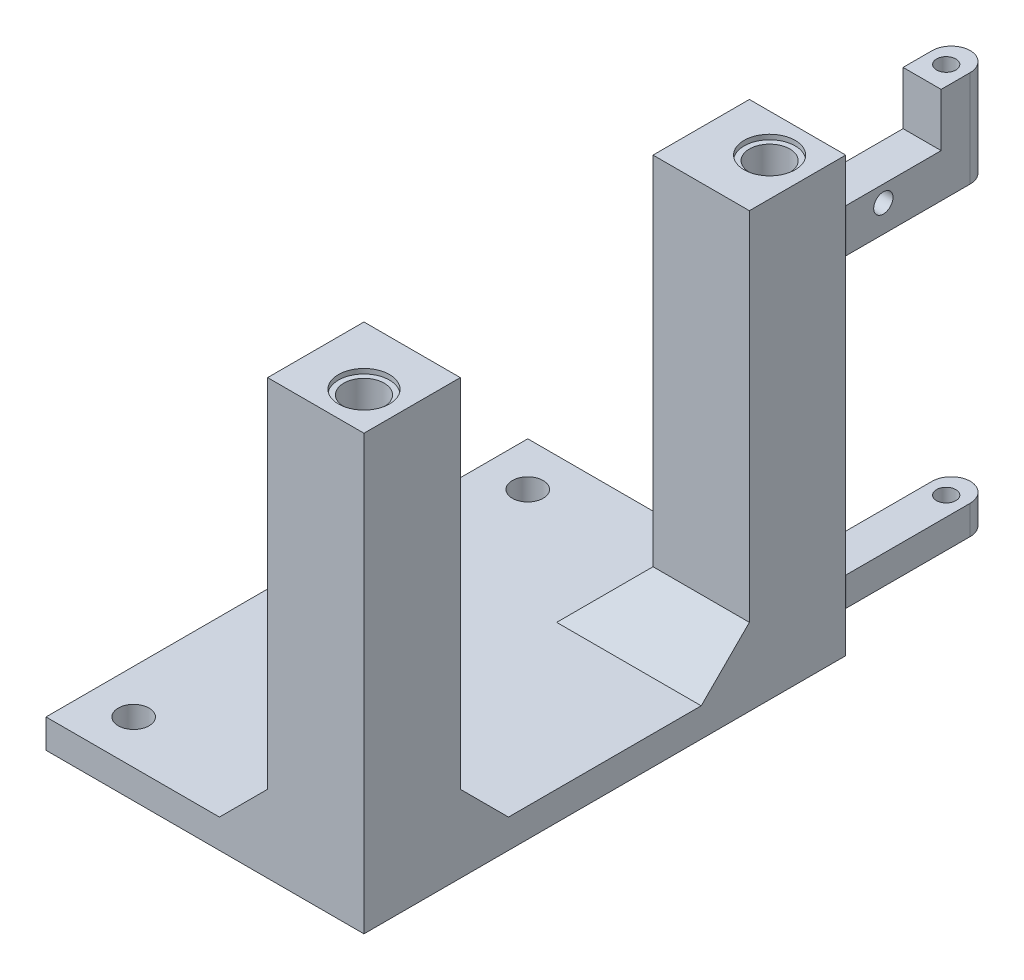
SolidWorks part; units mm, degrees
ref_plane "Front Plane" through (0, 0, 0) normal (0, 0, 1) x (1, 0, 0)
ref_plane "Top Plane" through (0, 0, 0) normal (0, 1, 0) x (1, 0, 0)
ref_plane "Right Plane" through (0, 0, 0) normal (1, 0, 0) x (0, 0, -1)
sketch "Sketch1" plane through (0, 0, 0) normal (0, 1, 0) x (1, 0, 0)
  line L1 (-6.5124, 9.686) -> (1.4876, 9.686)
  line L2 (-6.5124, 9.686) -> (-6.5124, -40.314)
  line L3 (-6.5124, -40.314) -> (1.4876, -40.314)
  line L4 (1.4876, 9.686) -> (1.4876, -40.314)
  line L5 (1.4876, 9.686) -> (26.4876, 9.686)
  line L6 (1.4876, 9.686) -> (1.4876, -40.314)
  line L7 (1.4876, -40.314) -> (26.4876, -40.314)
  line L8 (26.4876, 9.686) -> (26.4876, -40.314)
  circle A0 centre (-1.9624, -35.764) radius 1.6
  circle A1 centre (-1.9624, 5.136) radius 1.6
  dimension "D4" = 3.2
  dimension "D5" = 3.2
  dimension "D6" = 4.55
  dimension "D7" = 4.55
  dimension "D8" = 4.55
  dimension "D9" = 4.55
  dimension "D1" = 8
  dimension "D2" = 50
  dimension "D3" = 25
extrude "Boss-Extrude1" add sketch "Sketch1" along normal blind 3 contours A1 | A0 | L5 L8 L7 L3 L2 L1
sketch "Sketch2" plane through (0, 3, 0) normal (0, 1, 0) x (1, 0, 0)
  line L1 (26.4876, -40.314) -> (16.4876, -40.314)
  line L2 (26.4876, -40.314) -> (26.4876, -30.314)
  line L3 (26.4876, -30.314) -> (16.4876, -30.314)
  line L4 (16.4876, -40.314) -> (16.4876, -30.314)
  line L5 (26.4876, 9.686) -> (16.4876, 9.686)
  line L6 (26.4876, 9.686) -> (26.4876, -0.314)
  line L7 (26.4876, -0.314) -> (16.4876, -0.314)
  line L8 (16.4876, 9.686) -> (16.4876, -0.314)
  dimension "D1" = 10
  dimension "D2" = 10
  dimension "D3" = 10
  dimension "D4" = 10
extrude "Boss-Extrude2" add sketch "Sketch2" along normal blind 42
chamfer "Chamfer1" distance 5 angle 45 4 edges at (16.4876, 3, -4.686) (21.4876, 3, 0.314) (16.4876, 3, 35.314) (21.4876, 3, 30.314)
ref_plane "Plane1" through (0, 45, 0) normal (0, 1, 0) x (1, 0, 0)
sketch "Sketch3" plane through (0, 45, 0) normal (0, 1, 0) x (1, 0, 0)
  line L0 (26.4876, -40.314) -> (26.4876, -30.314) construction
  line L1 (16.4876, -40.314) -> (26.4876, -40.314) construction
  line L2 (26.4876, -0.314) -> (26.4876, 9.686) construction
  line L3 (26.4876, 9.686) -> (16.4876, 9.686) construction
  circle A0 centre (22.5376, -36.364) radius 2.1
  circle A1 centre (22.5376, 5.736) radius 2.1
  dimension "D1" = 4.2
  dimension "D3" = 3.95
  dimension "D4" = 4.2
  dimension "D6" = 3.95
  dimension "D2" = 3.95
  dimension "D5" = 3.95
extrude "Cut-Extrude1" cut sketch "Sketch3" against normal blind 52
sketch "Sketch4" plane through (0, 45, 0) normal (0, 1, 0) x (1, 0, 0)
  circle A0 centre (22.5376, -36.364) radius 2.65
  circle A1 centre (22.5376, 5.736) radius 2.65
  dimension "D1" = 5.3
  dimension "D2" = 5.3
extrude "Cut-Extrude2" cut sketch "Sketch4" against normal blind 0.5
ref_plane "Plane2" through (0, 22.5, 0) normal (0, -1, 0) x (-1, 0, 0)
mirror "Mirror1" about plane through (0, 22.5, 0) normal (0, -1, 0) of "Cut-Extrude2"
sketch "Sketch5" plane through (0, 0, -9.686) normal (0, 0, -1) x (-1, 0, 0)
  line L0 (-22.4876, 36.5) -> (-17.9876, 36.5) construction
  line L1 (-18.2876, 36.2) -> (-22.2399, 36.2)
  line L2 (-18.2876, 36.2) -> (-18.2876, 31.6868)
  line L3 (-18.2876, 31.6868) -> (-22.2399, 31.6868)
  line L4 (-22.2399, 36.2) -> (-22.2399, 31.6868)
  line L5 (-17.9876, 32.25) -> (-17.9876, 37) construction
  dimension "D1" = 0.3
  dimension "D2" = 0.3
extrude "Boss-Extrude3" add sketch "Sketch5" along normal up to surface (14.15 mm away)
sketch "Sketch6" plane through (22.2399, 0, 0) normal (1, 0, 0) x (0, 0, -1)
  circle A0 centre (17.836, 34.5) radius 1
  dimension "D1" = 2
extrude "Cut-Extrude3" cut sketch "Sketch6" against normal up to surface (3.9523 mm away) up to face at (18.2876, 33.9434, -16.761)
sketch "Sketch7" plane through (0, 0, -23.836) normal (0, 0, -1) x (-1, 0, 0)
  line L1 (-22.2399, 31.6868) -> (-18.2876, 31.6868)
  line L2 (-22.2399, 31.6868) -> (-22.2399, 41.7057)
  line L3 (-22.2399, 41.7057) -> (-18.2876, 41.7057)
  line L4 (-18.2876, 31.6868) -> (-18.2876, 41.7057)
  point P5 (-18.2876, 31.6868)
extrude "Boss-Extrude4" add sketch "Sketch7" along normal blind 5
sketch "Sketch8" plane through (0, 0, -9.686) normal (0, 0, -1) x (-1, 0, 0)
  line L0 (-18.2876, 41.7057) -> (-22.2399, 41.7057) construction
  line L1 (-22.2399, 36.2) -> (-18.2687, 36.2)
  line L2 (-22.2399, 36.2) -> (-22.2399, 41.7057)
  line L3 (-22.2399, 41.7057) -> (-18.2687, 41.7057)
  line L4 (-18.2687, 36.2) -> (-18.2687, 41.7057)
  point P5 (-18.2687, 36.2)
extrude "Boss-Extrude5" add sketch "Sketch8" along normal up to surface (2.15 mm away)
sketch "Sketch9" plane through (0, 0, -9.686) normal (0, 0, -1) x (-1, 0, 0)
  line L0 (6.5124, 0) -> (-26.4876, 0) construction
  line L1 (-22.2399, 0) -> (-18.2876, 0)
  line L2 (-22.2399, 0) -> (-22.2399, 3)
  line L3 (-22.2399, 3) -> (-18.2876, 3)
  line L4 (-18.2876, 0) -> (-18.2876, 3)
  line L5 (6.5124, 3) -> (-11.4876, 3) construction
  line L6 (-22.2399, 41.7057) -> (-22.2399, 31.6868) construction
  line L7 (-18.2876, 31.6868) -> (-18.2876, 41.7057) construction
extrude "Boss-Extrude6" add sketch "Sketch9" along normal up to surface (19.15 mm away) up to face at (20.2638, 36.6962, -28.836)
sketch "Sketch10" plane through (0, 41.7057, 0) normal (0, 1, 0) x (1, 0, 0)
  line L0 (18.2876, 23.836) -> (22.2399, 28.836) construction
  line L1 (18.2876, 28.836) -> (22.2399, 23.836) construction
  circle A0 centre (20.2638, 26.336) radius 1
  dimension "D1" = 2
extrude "Cut-Extrude4" cut sketch "Sketch10" against normal through all
fillet "Fillet3" radius 2 4 edges at (18.2876, 1.5, -28.836) (22.2399, 1.5, -28.836) (18.2876, 36.6962, -28.836) (22.2399, 36.6962, -28.836)
fillet "Fillet4" radius 4.25 1 edges at (22.2399, 1.5, -9.686)
fillet "Fillet5" radius 4.25 1 edges at (18.2876, 1.5, -9.686)
fillet "Fillet6" radius 4.25 1 edges at (22.2399, 36.6962, -9.686)
fillet "Fillet7" radius 4.25 1 edges at (18.2876, 33.9434, -9.686)
fillet "Fillet8" radius 1 1 edges at (20.2626, 3, -9.686)
fillet "Fillet9" radius 1 1 edges at (21.4876, 31.6868, -9.686)
sketch "Sketch11" plane through (0, 0, 40.314) normal (0, 0, 1) x (1, 0, 0)
  line L0 (16.4876, 45) -> (26.4876, 45) construction
  line L1 (18.4876, 45) -> (24.4876, 45)
  line L2 (18.4876, 45) -> (18.4876, 42)
  line L3 (18.4876, 42) -> (24.4876, 42)
  line L4 (24.4876, 45) -> (24.4876, 42)
  line L5 (-6.5124, 0) -> (26.4876, 0) construction
  line L6 (18.4876, 0) -> (24.4876, 0)
  line L7 (18.4876, 0) -> (18.4876, 3)
  line L8 (18.4876, 3) -> (24.4876, 3)
  line L9 (24.4876, 0) -> (24.4876, 3)
  line L10 (21.4876, 8) -> (21.4876, 0) construction
  line L11 (21.4876, 8) -> (21.4876, 45) construction
  line L13 (-6.5124, 3) -> (11.4876, 3) construction
  line L14 (16.4876, 8) -> (26.4876, 8) construction
  line L15 (26.4876, 8) -> (39.3241, 4.4212) construction
  line L16 (39.3241, 4.4212) -> (39.5028, 4.4212) construction
  dimension "D1" = 3
  dimension "D2" = 3
  dimension "D3" = 3
  dimension "D4" = 3
  dimension "D5" = 3
